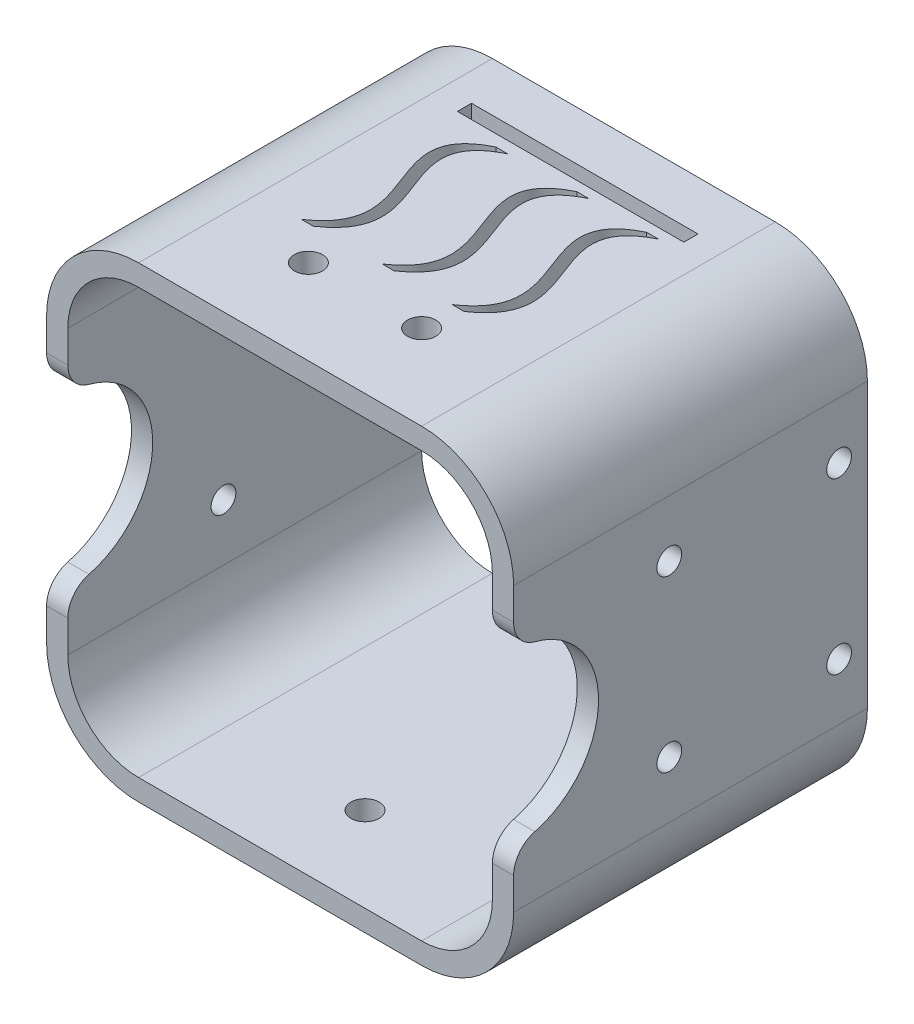
SolidWorks part; units mm, degrees
ref_plane "Piano frontale" through (0, 0, 0) normal (0, 0, 1) x (1, 0, 0)
ref_plane "Piano superiore" through (0, 0, 0) normal (0, 1, 0) x (1, 0, 0)
ref_plane "Piano destro" through (0, 0, 0) normal (1, 0, 0) x (0, 0, -1)
sketch "Schizzo1" plane through (0, 0, 0) normal (0, 0, 1) x (1, 0, 0)
  line L0 (-10, 0) -> (-50, 0)
  line L1 (0, -10) -> (0, -50)
  line L2 (-60, -10) -> (-60, -50)
  line L3 (-50, -60) -> (-10, -60)
  arc A0 (0, -50) -> (-10, -60) centre (-10, -50) cw
  arc A1 (-50, -60) -> (-60, -50) centre (-50, -50) cw
  arc A2 (0, -10) -> (-10, 0) centre (-10, -10) ccw
  arc A3 (-60, -10) -> (-50, 0) centre (-50, -10) cw
  point P7 (0, -60)
  point P10 (-60, -60)
  point P13 (0, 0)
  point P16 (-60, 0)
  dimension "D4" = 10
  dimension "D1" = 60
  dimension "D2" = 60
  dimension "D3" = 60
extrude "Estrusione-Sottile1" add sketch "Schizzo1" along normal blind 50 thin thin type one direction wall 3
sketch "Schizzo2" plane through (0, 3, 0) normal (0, 1, 0) x (1, 0, 0)
  line L0 (-30, 0) -> (-30, -50) construction
  line L1 (-10, 0) -> (-50, 0) construction
  line L2 (-10, -50) -> (-50, -50) construction
  circle A0 centre (-38, -38) radius 2
  circle A1 centre (-22, -38) radius 2
  dimension "D5" = 4
  dimension "D6" = 4
  dimension "D1" = 8
  dimension "D2" = 8
  dimension "D3" = 12
  dimension "D4" = 12
extrude "Taglio-Estrusione1" cut sketch "Schizzo2" against normal blind 10
sketch "Schizzo3" plane through (-63, 0, 0) normal (-1, 0, 0) x (0, 0, 1)
  line L0 (50, -10) -> (50, -50) construction
  circle A0 centre (50, -30) radius 12
  dimension "D1" = 24
extrude "Taglio-Estrusione2" cut sketch "Schizzo3" along direction (-1, 0, 0) on the side against the normal up to surface (66 mm away) up to face at (3, -30, 25)
fillet "Raccordo1" radius 4 1 edges at (-61.5, -18, 50) type face fillet first side face at (-30, -8.0394, 50) second side face at (-61.5, -30, 44)
fillet "Raccordo2" radius 4 1 edges at (-61.5, -42, 50) type face fillet first side face at (-61.5, -30.8513, 43.2978) second side face at (-30, -51.9606, 50)
fillet "Raccordo3" radius 4 1 edges at (1.5, -18, 50) type face fillet first side face at (1.5, -30, 44) second side face at (-30, -7.4574, 50)
fillet "Raccordo4" radius 4 1 edges at (1.5, -42, 50) type face fillet first side face at (1.5, -30.8513, 43.2978) second side face at (-30, -52.5426, 50)
sketch "Schizzo4" plane through (0, -63, 0) normal (0, -1, 0) x (1, 0, 0)
  line L0 (-30, 50) -> (-30, 0) construction
  line L1 (-50, 50) -> (-10, 50) construction
  line L2 (-50, 0) -> (-10, 0) construction
  circle A0 centre (-30, 38) radius 2
  dimension "D1" = 4
  dimension "D2" = 12
extrude "Taglio-Estrusione3" cut sketch "Schizzo4" against normal blind 10
sketch "Schizzo5" plane through (0, 3, 0) normal (0, 1, 0) x (1, 0, 0)
  line L0 (-30, 0) -> (-30, -50) construction
  line L1 (-46, -6.9458) -> (-14, -6.9458)
  line L2 (-46, -6.9458) -> (-46, -8.9458)
  line L3 (-46, -8.9458) -> (-14, -8.9458)
  line L4 (-14, -6.9458) -> (-14, -8.9458)
  line L5 (-10, 0) -> (-50, 0) construction
  line L6 (-10, -50) -> (-50, -50) construction
  line L7 (-30.9605, -32.9287) -> (-32.6391, -32.9195)
  line L8 (-26.0641, -10.3322) -> (-27.7428, -10.3231)
  line L9 (-42.1357, -33.1817) -> (-43.8144, -33.1725)
  line L10 (-37.2394, -10.5852) -> (-38.918, -10.576)
  line L11 (-21.0473, -32.9631) -> (-22.7259, -32.9539)
  line L12 (-16.1509, -10.3666) -> (-17.8296, -10.3574)
  spline S0 degree 3 poles (-16.1509, -10.3666) (-27.5731, -15.9557) (-10.2901, -25.7029) (-21.0473, -32.9631) knots 0 0 0 0 1 1 1 1
  spline S1 degree 3 poles (-17.8296, -10.3574) (-29.2518, -15.9465) (-11.9688, -25.6937) (-22.7259, -32.9539) knots 0 0 0 0 1 1 1 1
  spline S2 degree 3 poles (-26.0641, -10.3322) (-37.4863, -15.9213) (-20.2033, -25.6686) (-30.9605, -32.9287) knots 0 0 0 0 1 1 1 1
  spline S3 degree 3 poles (-27.7428, -10.3231) (-39.1649, -15.9122) (-21.882, -25.6594) (-32.6391, -32.9195) knots 0 0 0 0 1 1 1 1
  spline S4 degree 3 poles (-37.2394, -10.5852) (-48.6615, -16.1743) (-31.3786, -25.9215) (-42.1357, -33.1817) knots 0 0 0 0 1 1 1 1
  spline S5 degree 3 poles (-38.918, -10.576) (-50.3402, -16.1651) (-33.0573, -25.9123) (-43.8144, -33.1725) knots 0 0 0 0 1 1 1 1
  dimension "D1" = 16
  dimension "D2" = 16
  dimension "D3" = 2
extrude "Taglio-Estrusione4" cut sketch "Schizzo5" against normal blind 10
sketch "Schizzo7" plane through (-63, 0, 0) normal (-1, 0, 0) x (0, 0, 1)
  line L0 (0, -30) -> (38, -30) construction
  line L1 (0, -10) -> (0, -50) construction
  line L2 (0, -18) -> (47.951, -18) construction
  line L3 (0, -42) -> (47.951, -42) construction
  line L4 (16, -18) -> (16, -42) construction
  arc A0 (47, -18.381) -> (47, -41.619) centre (50, -30) ccw construction
  arc A1 (47, -18.381) -> (50, -14.5081) centre (46, -14.5081) ccw construction
  arc A2 (50, -45.4919) -> (47, -41.619) centre (46, -45.4919) ccw construction
  circle A3 centre (28, -18) radius 1.75
  circle A4 centre (28, -42) radius 1.75
  circle A5 centre (4, -42) radius 1.75
  circle A6 centre (4, -18) radius 1.75
  dimension "D4" = 3.5
  dimension "D1" = 12
  dimension "D2" = 12
  dimension "D3" = 16
  dimension "D5" = 12
extrude "Taglio-Estrusione5" cut sketch "Schizzo7" against normal up to surface (66 mm away) up to face at (3, -30, 35.7906)
